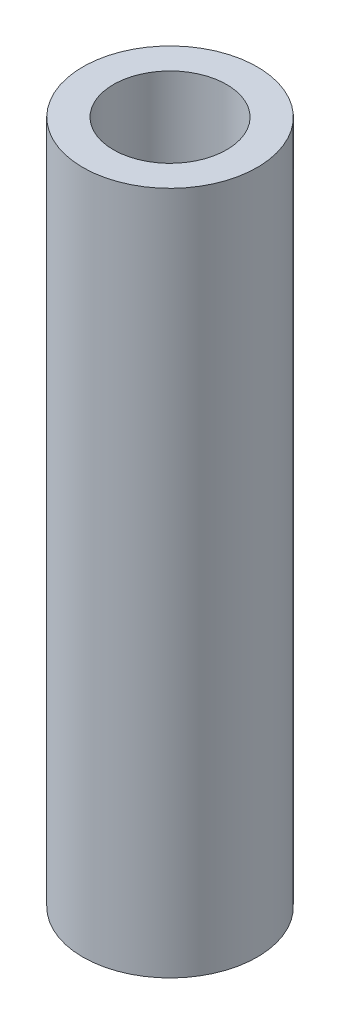
SolidWorks part; units mm, degrees
material "ABS"
ref_plane "Front Plane" through (0, 0, 0) normal (0, 0, 1) x (1, 0, 0)
ref_plane "Top Plane" through (0, 0, 0) normal (0, 1, 0) x (1, 0, 0)
ref_plane "Right Plane" through (0, 0, 0) normal (1, 0, 0) x (0, 0, -1)
sketch "Sketch1" plane through (0, 0, 0) normal (0, 1, 0) x (1, 0, 0)
  circle A0 centre (0, 0) radius 18.5
  circle A1 centre (0, 0) radius 28.5
  dimension "D1" = 37
  dimension "D2" = 57
extrude "Boss-Extrude1" add sketch "Sketch1" along normal blind 223.5
sketch "Sketch2" plane through (0, 0, 0) normal (1, 0, 0) x (0, 0, -1)
  line L0 (18.5, 223.5) -> (-18.5, 223.5) construction
  circle A0 centre (0, 158.8) radius 12.53
  circle A1 centre (0, 98.8) radius 12.53
  circle A2 centre (0, 38.8) radius 12.53
  dimension "D1" = 25.06
  dimension "D2" = 25.06
  dimension "D3" = 25.06
  dimension "D4" = 64.7
  dimension "D5" = 60
  dimension "D6" = 60
extrude "Cut-Extrude1" cut sketch "Sketch2" against normal through all
